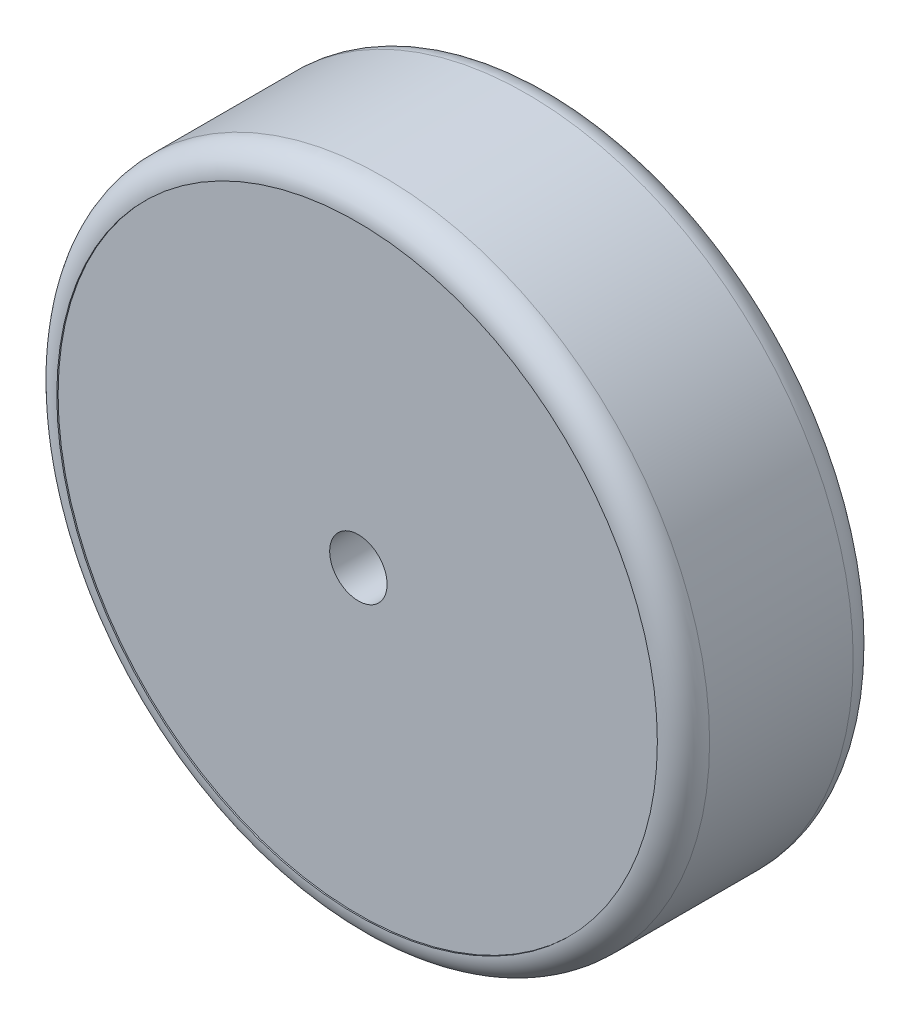
SolidWorks part; units mm, degrees
ref_plane "Front Plane" through (0, 0, 0) normal (0, 0, 1) x (1, 0, 0)
ref_plane "Top Plane" through (0, 0, 0) normal (0, 1, 0) x (1, 0, 0)
ref_plane "Right Plane" through (0, 0, 0) normal (1, 0, 0) x (0, 0, -1)
sketch "Sketch1" plane through (0, 0, 0) normal (0, 0, 1) x (1, 0, 0)
  line L0 (0, 0) -> (0, 25)
  circle A0 centre (0, 0) radius 25
  dimension "D1" = 50
extrude "Boss-Extrude1" add sketch "Sketch1" along normal blind 15 contours A0
fillet "Fillet1" radius 2 2 edges at (25, 0, 15) (25, 0, 0)
sketch "Sketch7" plane through (0, 0, 15) normal (0, 0, 1) x (1, 0, 0)
  circle A0 centre (0, 0) radius 2.2
  dimension "D1" = 4.4
extrude "Cut-Extrude2" cut sketch "Sketch7" along normal through all and the other way through all
ref_plane "Plane1" through (0, 0, 7.5) normal (0, 0, -1) x (-1, 0, 0)
sketch "Sketch8" plane through (0, 0, 15) normal (0, 0, 1) x (1, 0, 0)
  circle A0 centre (0, 0) radius 23
  dimension "D1" = 46
extrude "Cut-Extrude3" cut sketch "Sketch8" against normal blind 0.1
sketch "Sketch9" plane through (0, 0, 0) normal (0, 0, -1) x (-1, 0, 0)
  circle A0 centre (0, 0) radius 23
  dimension "D1" = 46
extrude "Cut-Extrude4" cut sketch "Sketch9" against normal blind 0.1
sketch "Sketch10" plane through (0, 0, 0.1) normal (0, 0, -1) x (-1, 0, 0)
  circle A0 centre (0, 0) radius 23
  dimension "D1" = 46
extrude "Boss-Extrude3" add sketch "Sketch10" against normal blind 0.1
sketch "Sketch11" plane through (0, 0, 7.5) normal (0, 0, -1) x (-1, 0, 0)
  circle A0 centre (0, 0) radius 2.2
  dimension "D1" = 4.4
extrude "Cut-Extrude5" cut sketch "Sketch11" along normal through all
sketch "Sketch12" plane through (0, 0, 14.9) normal (0, 0, 1) x (1, 0, 0)
  circle A0 centre (0, 0) radius 23
  dimension "D1" = 46
extrude "Boss-Extrude4" add sketch "Sketch12" against normal blind 0.1
sketch "Sketch13" plane through (0, 0, 0.1) normal (0, 0, -1) x (-1, 0, 0)
  circle A0 centre (0, 0) radius 2.2
extrude "Cut-Extrude6" cut sketch "Sketch13" against normal through all
